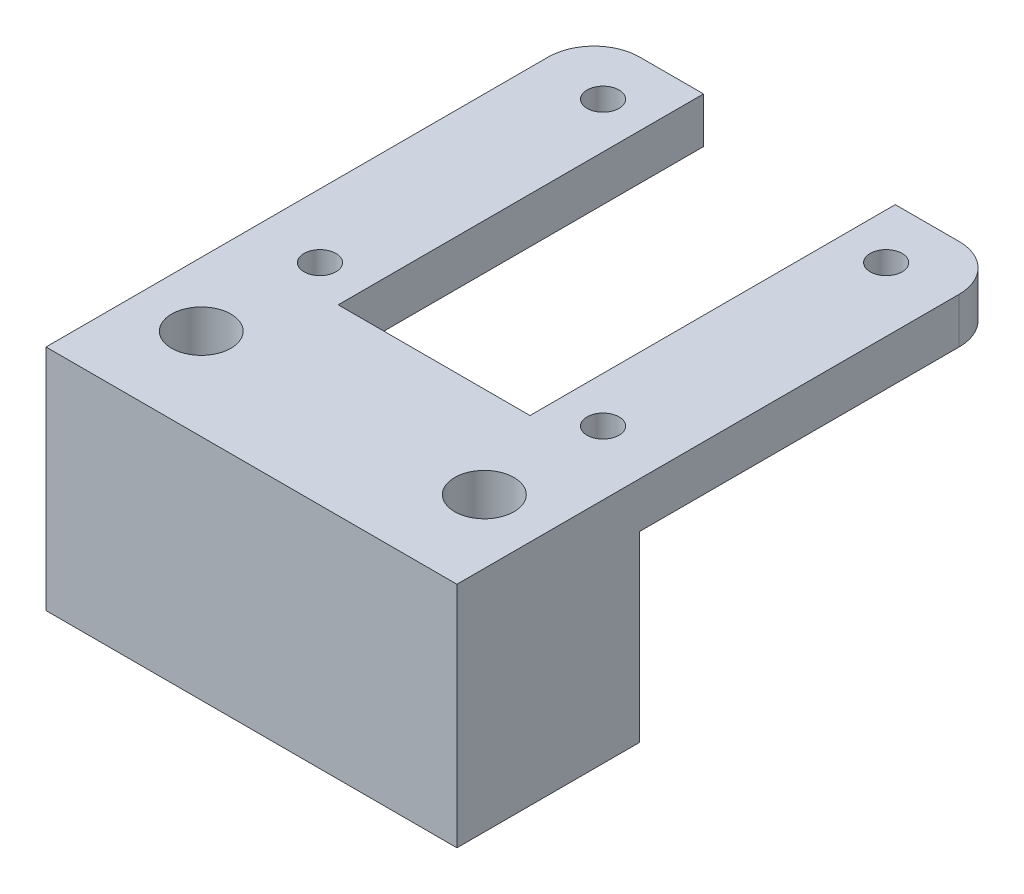
SolidWorks part; units mm, degrees
material "ABS"
ref_plane "Front Plane" through (0, 0, 0) normal (0, 0, 1) x (1, 0, 0)
ref_plane "Top Plane" through (0, 0, 0) normal (0, 1, 0) x (1, 0, 0)
ref_plane "Right Plane" through (0, 0, 0) normal (1, 0, 0) x (0, 0, -1)
sketch "Sketch1" plane through (0, 0, 0) normal (0, 1, 0) x (1, 0, 0)
  line L1 (-22.5, -10) -> (22.5, -10)
  line L2 (-22.5, -10) -> (-22.5, 10)
  line L3 (-22.5, 10) -> (22.5, 10)
  line L4 (22.5, -10) -> (22.5, 10)
  line L5 (-22.5, -10) -> (22.5, 10) construction
  line L6 (-22.5, 10) -> (22.5, -10) construction
  point P0 (0, 0)
  dimension "D1" = 20
  dimension "D2" = 45
extrude "Boss-Extrude1" add sketch "Sketch1" along normal blind 25
sketch "Sketch2" plane through (0, 0, -10) normal (0, 0, -1) x (-1, 0, 0)
  line L0 (-22.5, 25) -> (-22.5, 0) construction
  line L1 (-22.5, 25) -> (-10.5, 25)
  line L2 (-22.5, 25) -> (-22.5, 20)
  line L3 (-22.5, 20) -> (-10.5, 20)
  line L4 (-10.5, 25) -> (-10.5, 20)
  line L5 (-22.5, 25) -> (22.5, 25) construction
  line L11 (22.5, 25) -> (10.5, 25)
  line L12 (22.5, 25) -> (22.5, 20)
  line L13 (22.5, 20) -> (10.5, 20)
  line L14 (10.5, 25) -> (10.5, 20)
  dimension "D1" = 5
  dimension "D2" = 12
  dimension "D3" = 12
  dimension "D4" = 5
extrude "Boss-Extrude2" add sketch "Sketch2" along normal blind 40
sketch "Sketch3" plane through (0, 25, 0) normal (0, 1, 0) x (1, 0, 0)
  line L1 (22.5, -10) -> (22.5, 50) construction
  line L2 (10.5, 10) -> (-10.5, 10) construction
  circle A0 centre (15.5, 44) radius 1.75
  circle A1 centre (15.5, 13) radius 1.75
  circle A2 centre (-15.5, 13) radius 1.75
  circle A3 centre (-15.5, 44) radius 1.75
  dimension "D1" = 3.5
  dimension "D3" = 3.5
  dimension "D6" = 3.5
  dimension "D7" = 3.5
  dimension "D2" = 7
  dimension "D4" = 3
  dimension "D5" = 31
  dimension "D8" = 31
extrude "Cut-Extrude1" cut sketch "Sketch3" against normal through all
sketch "Sketch4" plane through (0, 25, 0) normal (0, 1, 0) x (1, 0, 0)
  line L0 (22.5, -10) -> (22.5, 50) construction
  line L1 (-22.5, 50) -> (-22.5, -10) construction
  circle A0 centre (-15.5, 0) radius 1.75
  circle A1 centre (15.5, 0) radius 1.75
  dimension "D1" = 3.5
  dimension "D2" = 3.5
  dimension "D3" = 7
  dimension "D4" = 7
extrude "Cut-Extrude2" cut sketch "Sketch4" against normal blind 25
hole_wizard "CBORE for M3 Hex Socket Head Cap Screw1" positions "Sketch5" profile "Sketch6" counterbore size "M3" standard "ISO" end condition through all
sketch "Sketch5" plane through (0, 25, 0) normal (0, 1, 0) x (1, 0, 0)
  point P0 (15.5, 0)
  point P3 (-15.5, 0)
sketch "Sketch6" plane through (15.5, 25, 0) normal (1, 0, 0) x (0, 0, 1)
  line L0 (0, 0) -> (0, 25)
  line L1 (0, 25) -> (1.7, 25)
  line L3 (1.7, 25) -> (1.7, 11.4)
  line L4 (1.7, 11.4) -> (3.25, 11.4)
  line L5 (3.25, 11.4) -> (3.25, 0)
  line L7 (3.25, 0) -> (0, 0)
  line L11 (0, -6.35) -> (0, 107.95) construction
  dimension "Thru Hole Dia." = 3.4
  dimension "Thru Hole Depth" = 25
  dimension "C'Bore Dia." = 6.5
  dimension "C'Bore Depth" = 11.4
hole_wizard "CBORE for M3 Hex Socket Head Cap Screw2" positions "Sketch7" profile "Sketch8" counterbore size "M3" standard "ISO" end condition through all
sketch "Sketch7" plane through (0, 20, 0) normal (0, -1, 0) x (-1, 0, 0)
  point P0 (15.5, 44)
  point P3 (15.5, 13)
  point P6 (-15.5, 13)
  point P9 (-15.5, 44)
sketch "Sketch8" plane through (-15.5, 20, -44) normal (1, 0, 0) x (0, 0, -1)
  line L0 (0, 0) -> (0, 5)
  line L1 (0, 5) -> (1.7, 5)
  line L3 (1.7, 5) -> (1.7, 2)
  line L4 (1.7, 2) -> (3.25, 2)
  line L5 (3.25, 2) -> (3.25, 0)
  line L7 (3.25, 0) -> (0, 0)
  line L11 (0, -6.35) -> (0, 107.95) construction
  dimension "Thru Hole Dia." = 3.4
  dimension "Thru Hole Depth" = 5
  dimension "C'Bore Dia." = 6.5
  dimension "C'Bore Depth" = 2
fillet "Fillet1" radius 5 2 edges at (22.5, 22.5, -50) (-22.5, 22.5, -50)
